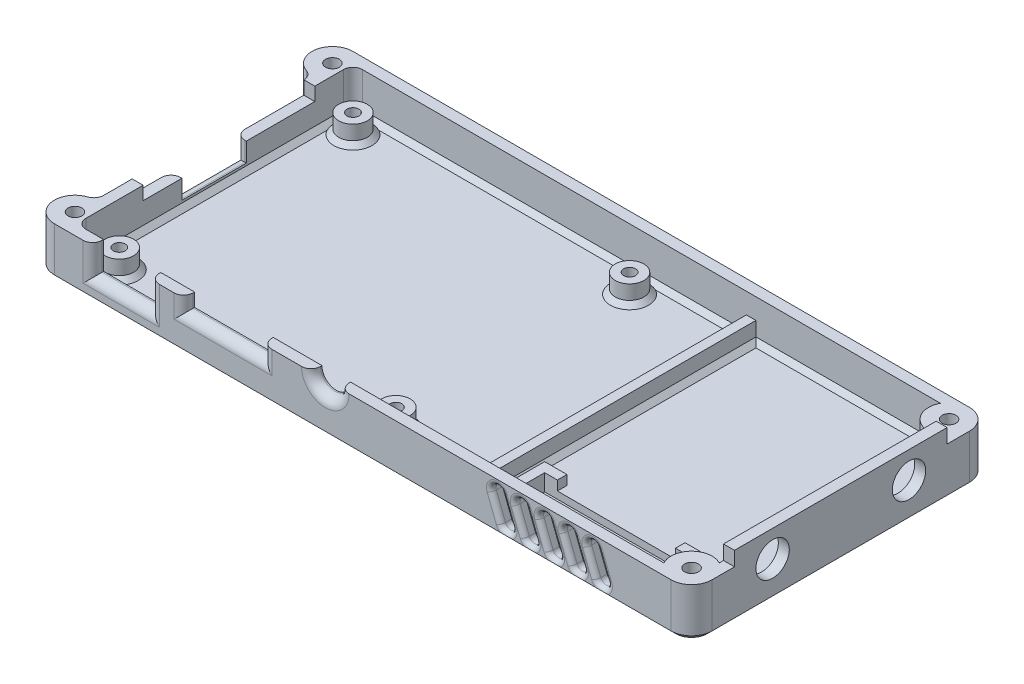
SolidWorks part; units mm, degrees
ref_plane "Front Plane" through (0, 0, 0) normal (0, 0, 1) x (1, 0, 0)
ref_plane "Top Plane" through (0, 0, 0) normal (0, 1, 0) x (1, 0, 0)
ref_plane "Right Plane" through (0, 0, 0) normal (1, 0, 0) x (0, 0, -1)
sketch "Sketch1" plane through (0, 0, 0) normal (0, 1, 0) x (1, 0, 0)
  line L0 (-71.5618, 3.106) -> (55.4382, 3.106) construction
  line L1 (-71.5618, 31.106) -> (55.4382, 31.106)
  line L2 (-71.5618, 31.106) -> (-71.5618, -24.894)
  line L3 (-71.5618, -24.894) -> (55.4382, -24.894)
  line L4 (55.4382, 31.106) -> (55.4382, -24.894)
  line L5 (-60.6618, -24.894) -> (-60.6618, -31.6828) construction
  line L6 (-68.0618, 27.606) -> (-10.0618, 27.606)
  line L7 (-68.0618, 27.606) -> (-68.0618, -21.394)
  line L8 (-68.0618, -21.394) -> (-10.0618, -21.394)
  line L9 (-10.0618, 27.606) -> (-10.0618, -21.394)
  line L10 (-39.5618, -24.894) -> (-39.5618, -31.6828) construction
  line L11 (-18.0618, -24.894) -> (-18.0618, -31.6828) construction
  line L12 (-65.4118, -26.5648) -> (-55.9118, -26.5648) construction
  line L13 (-48.0618, -26.5648) -> (-31.0618, -26.5648) construction
  line L14 (-22.0618, -26.5648) -> (-14.0618, -26.5648) construction
  line L15 (-72.5618, 9.606) -> (-72.5618, -3.394) construction
  line L16 (-71.5618, 3.106) -> (-72.5618, 3.106) construction
  dimension "D1" = 127
  dimension "D2" = 56
  dimension "D3" = 49
  dimension "D4" = 58
  dimension "D5" = 3.5
  dimension "D6" = 3.5
  dimension "D7" = 10.9
  dimension "D8" = 32
  dimension "D9" = 53.5
  dimension "D10" = 2
  dimension "D11" = 13
  dimension "D12" = 9.5
  dimension "D13" = 17
  dimension "D14" = 8
sketch "Sketch3" plane through (0, 0, 0) normal (0, 1, 0) x (1, 0, 0)
  line L4 (58.7382, 34.406) -> (-74.8618, 34.406)
  line L5 (-74.8618, 34.406) -> (-74.8618, -28.194)
  line L6 (-74.8618, -28.194) -> (58.7382, -28.194)
  line L7 (58.7382, -28.194) -> (58.7382, 34.406)
  line L8 (56.4382, 32.106) -> (-72.5618, 32.106)
  line L9 (56.4382, -25.894) -> (56.4382, 32.106)
  line L10 (-72.5618, -25.894) -> (56.4382, -25.894)
  line L11 (-72.5618, 32.106) -> (-72.5618, -25.894)
  line L12 (56.4382, 32.106) -> (-72.5618, 32.106)
  line L13 (56.4382, -25.894) -> (56.4382, 32.106)
  line L14 (-72.5618, -25.894) -> (56.4382, -25.894)
  line L15 (-72.5618, 32.106) -> (-72.5618, -25.894)
  line L16 (-8.0618, 3.106) -> (-8.0618, 34.406) construction
  line L17 (-71.5618, 3.106) -> (55.4382, 3.106) construction
  line L20 (-74.8618, 3.106) -> (52.7382, 3.106) construction
  line L25 (58.7382, -28.194) -> (58.7382, 34.406) construction
  line L26 (56.4382, -25.894) -> (56.4382, 32.106) construction
  dimension "D1" = 1
  dimension "D2" = 2.3
extrude "Boss-Extrude1" add sketch "Sketch3" along normal blind 10.3
sketch "Sketch5" plane through (0, 0, 0) normal (0, 1, 0) x (1, 0, 0)
  line L1 (-72.5618, 32.106) -> (56.4382, 32.106)
  line L2 (-72.5618, 32.106) -> (-72.5618, -25.894)
  line L3 (-72.5618, -25.894) -> (56.4382, -25.894)
  line L4 (56.4382, 32.106) -> (56.4382, -25.894)
extrude "Boss-Extrude2" add sketch "Sketch5" along normal blind 2
sketch "Sketch6" plane through (0, 2, 0) normal (0, 1, 0) x (1, 0, 0)
  circle A0 centre (-68.0618, 27.606) radius 3
  circle A1 centre (-68.0618, -21.394) radius 3
  circle A2 centre (-10.0618, -21.394) radius 3
  circle A3 centre (-10.0618, 27.606) radius 3
extrude "Boss-Extrude3" add sketch "Sketch6" along normal blind 4
hole_wizard "Ø2.5 (2.5) Diameter Hole1" positions "Sketch8" profile "Sketch9" hole size "Ø2.5" standard "ANSI Metric"
sketch "Sketch8" plane through (0, 6, 0) normal (0, 1, 0) x (1, 0, 0)
  point P0 (-68.0618, 27.606)
  point P3 (-10.0618, 27.606)
  point P6 (-10.0618, -21.394)
  point P9 (-68.0618, -21.394)
sketch "Sketch9" plane through (-68.0618, 6, -27.606) normal (1, 0, 0) x (0, 0, 1)
  line L0 (0, 0) -> (0, 8.7511)
  line L1 (0, 8.7511) -> (1.25, 8)
  line L2 (1.25, 8) -> (1.25, 0)
  line L5 (1.25, 0) -> (0, 0)
  line L10 (0, 8.7511) -> (-1.25, 8) construction
  line L11 (0, -6.35) -> (0, 107.95) construction
  dimension "Hole Dia." = 2.5
  dimension "Hole Depth" = 8
  dimension "Drill Angle" = 118
sketch "Sketch10" plane through (0, 2, 0) normal (0, 1, 0) x (1, 0, 0)
  line L0 (56.4382, 32.106) -> (-72.5618, 32.106) construction
  line L1 (9.9382, 32.106) -> (11.9382, 32.106)
  line L2 (9.9382, 32.106) -> (9.9382, -25.894)
  line L3 (9.9382, -25.894) -> (11.9382, -25.894)
  line L4 (11.9382, 32.106) -> (11.9382, -25.894)
  line L5 (-72.5618, -25.894) -> (56.4382, -25.894) construction
  line L6 (-10.0618, 27.606) -> (-10.0618, -21.394) construction
  dimension "D1" = 2
  dimension "D2" = 20
extrude "Boss-Extrude4" add sketch "Sketch10" along normal blind 4
sketch "Sketch11" plane through (0, 0, 28.194) normal (0, 0, 1) x (1, 0, 0)
  line L0 (-74.8618, 10.3) -> (-74.8618, 0) construction
  line L1 (-66.8618, 10.3) -> (-54.8618, 10.3)
  line L2 (-66.8618, 10.3) -> (-66.8618, 4.5)
  line L3 (-66.8618, 4.5) -> (-54.8618, 4.5)
  line L4 (-54.8618, 10.3) -> (-54.8618, 4.5)
  line L5 (-74.8618, 0) -> (58.7382, 0) construction
  line L6 (-60.8618, 10.3) -> (-60.6618, 0) construction
  line L7 (-65.4118, 0) -> (-55.9118, 0) construction
  line L9 (-47.778, 10.3) -> (-31.278, 10.3)
  line L10 (-47.778, 10.3) -> (-47.778, 7.5)
  line L11 (-47.778, 7.5) -> (-31.278, 7.5)
  line L12 (-31.278, 10.3) -> (-31.278, 7.5)
  line L13 (-68.0618, 0) -> (-10.0618, 0) construction
  line L14 (-39.5618, 0) -> (-39.528, 10.3) construction
  line L15 (-48.0618, 0) -> (-31.0618, 0) construction
  line L16 (-18.0618, 0) -> (-18.0618, 10.3) construction
  line L17 (-22.0618, 0) -> (-14.0618, 0) construction
  line L18 (-74.8618, 10.3) -> (58.7382, 10.3) construction
  circle A0 centre (-18.0618, 10.3) radius 3
  dimension "D5" = 6
  dimension "D1" = 4.5
  dimension "D2" = 12
  dimension "D3" = 7.5
  dimension "D4" = 16.5
  dimension "D6" = 8
extrude "Cut-Extrude1" cut sketch "Sketch11" against normal up to next
sketch "Sketch12" plane through (-74.8618, 0, 0) normal (-1, 0, 0) x (0, 0, 1)
  line L0 (-3.106, 0) -> (-3.106, 10.3) construction
  line L1 (-27.606, 0) -> (21.394, 0) construction
  line L2 (-34.406, 10.3) -> (28.194, 10.3) construction
  line L4 (-9.7329, 10.3) -> (3.7671, 10.3)
  line L5 (-9.7329, 10.3) -> (-9.7329, 3.5)
  line L6 (-9.7329, 3.5) -> (3.7671, 3.5)
  line L7 (3.7671, 10.3) -> (3.7671, 3.5)
  line L8 (-24.106, 10.3) -> (11.894, 10.3)
  line L9 (-24.106, 10.3) -> (-24.106, 7.5)
  line L10 (-24.106, 7.5) -> (11.894, 7.5)
  line L11 (11.894, 10.3) -> (11.894, 7.5)
  dimension "D1" = 13.5
  dimension "D2" = 3.5
  dimension "D3" = 7.5
  dimension "D4" = 36
extrude "Cut-Extrude2" cut sketch "Sketch12" against normal up to next contours L10 L11 L8 L9 | L7 L6 L5 L4
fillet "Fillet6" radius 2 1 edges at (56.4382, 6.15, -32.106)
fillet "Fillet8" radius 2 2 edges at (-72.5618, 6.15, 25.894) (-72.5618, 6.15, -32.106)
chamfer "Chamfer1" distance 1 angle 45 4 edges at (-68.0618, 2, 24.394) (-10.0618, 2, 24.394) (-10.0618, 2, -24.606) (-68.0618, 2, -24.606)
fillet "Fillet9" radius 2 9 edges at (-74.8618, 5.5, -9.7329) (-74.8618, 3.5, -2.9829) (-74.8618, 5.5, 3.7671) (-18.0618, 7.3, 28.194) (-31.278, 8.9, 28.194) (-47.778, 8.9, 28.194) (-39.528, 7.5, 28.194) (-54.8618, 7.4, 28.194) (-60.8618, 4.5, 28.194)
sketch "Sketch13" plane through (58.7382, 0, -61.1442) normal (1, 0, 0) x (0, 0, -1)
  line L0 (-89.3382, 10.3) -> (-89.3382, 0) construction
  line L1 (-26.7382, 10.3) -> (-26.7382, 0) construction
  circle A0 centre (-72.3382, 7.7223) radius 3.5
  circle A1 centre (-43.7382, 7.7223) radius 3.5
  dimension "D1" = 17
  dimension "D2" = 17
sketch "Sketch17" plane through (0, 0, 0) normal (0, 1, 0) x (1, 0, 0)
  line L0 (-74.8618, 34.406) -> (-74.8618, 24.106) construction
  line L1 (-74.8618, 34.406) -> (-74.8618, 25.806)
  line L2 (-74.8618, 25.806) -> (-74.659, 25.9406)
  line L3 (-74.8618, -19.594) -> (-74.8618, -28.194)
  line L4 (-74.8618, -28.194) -> (-74.659, -28.0594)
  arc A0 (-74.8618, -19.594) -> (-74.8618, -28.194) centre (-74.8618, -23.894) ccw
  arc A1 (-74.8618, 34.406) -> (-74.8618, 25.806) centre (-74.8618, 30.106) ccw
extrude "Boss-Extrude6" add sketch "Sketch17" along normal up to vertex (10.3 mm away) contours L1 A1 | L3 A0 region at (-76.6867, 0, -30.106) region at (-76.6867, 0, 23.894) up to point (-74.8618, 10.3, 28.194)
hole_wizard "Ø2.9 (2.9) Diameter Hole2" positions "Sketch19" profile "Sketch18" hole size "Ø2.9" standard "ANSI Metric" end condition up to next
sketch "Sketch19" plane through (0, 10.3, 0) normal (0, 1, 0) x (1, 0, 0)
  point P0 (-74.8618, 30.106)
sketch "Sketch18" plane through (-74.8618, 10.3, -30.106) normal (1, 0, 0) x (0, 0, 1)
  line L0 (0, 0) -> (0, 10.3)
  line L1 (0, 10.3) -> (1.45, 10.3)
  line L2 (1.45, 10.3) -> (1.45, 0)
  line L5 (1.45, 0) -> (0, 0)
  line L11 (0, -6.35) -> (0, 107.95) construction
  dimension "Thru Hole Dia." = 2.9
  dimension "Thru Hole Depth" = 10.3
hole_wizard "Ø2.9 (2.9) Diameter Hole1" positions "Sketch21" profile "Sketch20" hole size "Ø2.9" standard "ANSI Metric" end condition up to next
sketch "Sketch21" plane through (0, 10.3, 0) normal (0, 1, 0) x (1, 0, 0)
  point P0 (-74.8618, -23.894)
sketch "Sketch20" plane through (-74.8618, 10.3, 23.894) normal (1, 0, 0) x (0, 0, 1)
  line L0 (0, 0) -> (0, 10.3)
  line L1 (0, 10.3) -> (1.45, 10.3)
  line L2 (1.45, 10.3) -> (1.45, 0)
  line L5 (1.45, 0) -> (0, 0)
  line L11 (0, -6.35) -> (0, 107.95) construction
  dimension "Thru Hole Dia." = 2.9
  dimension "Thru Hole Depth" = 10.3
sketch "Sketch24" plane through (0, 2, 0) normal (0, 1, 0) x (1, 0, 0)
  line L0 (11.9382, 3.106) -> (61.5789, 3.106) construction
  line L1 (11.9382, -25.894) -> (11.9382, 32.106) construction
  line L2 (58.7382, -28.194) -> (58.7382, 34.406) construction
  circle A0 centre (54.4382, -23.894) radius 4.3
  circle A1 centre (54.4382, 30.106) radius 4.3
  dimension "D1" = 4.3
extrude "Boss-Extrude7" add sketch "Sketch24" along normal up to surface (8.3 mm away) up to face at (-74.8618, 10.3, 25.344)
hole_wizard "Ø2.9 (2.9) Diameter Hole5" positions "Sketch31" profile "Sketch30" hole size "Ø2.9" standard "ANSI Metric" end condition up to next
sketch "Sketch31" plane through (0, 10.3, 0) normal (0, 1, 0) x (1, 0, 0)
  point P0 (54.4382, -23.894)
sketch "Sketch30" plane through (54.4382, 10.3, 23.894) normal (1, 0, 0) x (0, 0, 1)
  line L0 (0, 0) -> (0, 10.3)
  line L1 (0, 10.3) -> (1.45, 10.3)
  line L2 (1.45, 10.3) -> (1.45, 0)
  line L5 (1.45, 0) -> (0, 0)
  line L11 (0, -6.35) -> (0, 107.95) construction
  dimension "Thru Hole Dia." = 2.9
  dimension "Thru Hole Depth" = 10.3
hole_wizard "Ø2.9 (2.9) Diameter Hole4" positions "Sketch28" profile "Sketch27" hole size "Ø2.9" standard "ANSI Metric" end condition up to next
sketch "Sketch28" plane through (0, 10.3, 0) normal (0, 1, 0) x (1, 0, 0)
  point P0 (54.4382, 30.106)
sketch "Sketch27" plane through (54.4382, 10.3, -30.106) normal (1, 0, 0) x (0, 0, 1)
  line L0 (0, 0) -> (0, 10.3)
  line L1 (0, 10.3) -> (1.45, 10.3)
  line L2 (1.45, 10.3) -> (1.45, 0)
  line L5 (1.45, 0) -> (0, 0)
  line L11 (0, -6.35) -> (0, 107.95) construction
  dimension "Thru Hole Dia." = 2.9
  dimension "Thru Hole Depth" = 10.3
fillet "Fillet10" radius 4.3 1 edges at (58.7382, 5.15, -34.406)
fillet "Fillet18" radius 2 2 edges at (-74.8618, 5.15, 19.594) (-74.8618, 5.15, -25.806)
chamfer "Chamfer3" distance 1 angle 45 9 edges at (57.4788, 0, -33.1466) (-10.2118, 0, -34.406) (58.7382, 0, -0.956) (-79.1058, 0, -30.7975) (-75.2385, 0, -25.3002) (-74.8618, 0, -3.106) (-75.2385, 0, 19.0883) (-79.1058, 0, 24.5855) (-8.0618, 0, 28.194)
fillet "Fillet19" radius 2 1 edges at (-66.8618, 6.4, 28.194)
fillet "Fillet20" radius 4.3 1 edges at (58.7382, 5.65, 28.194)
chamfer "Chamfer5" distance 1 angle 45 8 edges at (-72.5618, 2, -3.106) (-71.976, 2, 25.3082) (-71.976, 2, -31.5202) (-30.3118, 2, 25.894) (-30.3118, 2, -32.106) (9.9382, 2, -3.106) (11.9382, 2, -3.106) (31.2849, 2, -32.106)
chamfer "Chamfer6" distance 1 angle 45 1 edges at (56.4382, 2, -3.106)
sketch "Sketch29" plane through (0, 10.3, 0) normal (0, 1, 0) x (1, 0, 0)
  line L0 (56.4382, -20.0874) -> (56.4382, 26.2994) construction
  line L1 (56.4382, 25.406) -> (58.7382, 25.406)
  line L2 (56.4382, 25.406) -> (56.4382, -19.194)
  line L3 (56.4382, -19.194) -> (58.7382, -19.194)
  line L4 (58.7382, 25.406) -> (58.7382, -19.194)
  line L5 (58.7382, -23.894) -> (58.7382, 30.106) construction
  line L6 (54.4382, 34.406) -> (-74.8618, 34.406) construction
  line L7 (-13.0618, -28.194) -> (54.4382, -28.194) construction
  dimension "D1" = 9
  dimension "D2" = 9
extrude "Boss-Extrude8" add sketch "Sketch29" along normal blind 3
extrude "Cut-Extrude3" cut sketch "Sketch13" against normal up to next
sketch "Sketch32" plane through (0, 2, 0) normal (0, 1, 0) x (1, 0, 0)
  line L0 (12.9382, -25.894) -> (50.6317, -25.894) construction
  line L1 (15.4382, -15.694) -> (45.5382, -15.694)
  line L2 (15.4382, -15.694) -> (15.4382, -25.894)
  line L3 (15.4382, -25.894) -> (45.5382, -25.894)
  line L4 (45.5382, -15.694) -> (45.5382, -25.894)
  line L5 (-72.5618, -23.894) -> (-72.5618, 30.106) construction
  dimension "D1" = 10.2
  dimension "D2" = 30.1
  dimension "D3" = 88
extrude "Cut-Extrude4" cut sketch "Sketch32" against normal blind 1.5
sketch "Sketch33" plane through (0, 2, 0) normal (0, 1, 0) x (1, 0, 0)
  line L0 (15.4382, -15.694) -> (15.4382, -25.894)
  line L2 (15.4382, -25.894) -> (13.4382, -25.894)
  line L3 (12.9382, -25.894) -> (15.4382, -25.894) construction
  line L4 (47.5382, -13.694) -> (47.5382, -20.8822)
  line L5 (47.5382, -20.8822) -> (45.5382, -20.8822)
  line L6 (45.5382, -25.894) -> (45.5382, -20.7012) construction
  line L7 (45.5382, -20.8822) -> (45.5382, -15.694)
  line L8 (30.4882, -15.694) -> (30.4882, -23.4127) construction
  line L9 (45.5382, -15.694) -> (15.4382, -15.694) construction
  line L10 (18.1083, -13.694) -> (18.1083, -15.694)
  line L11 (42.8681, -13.694) -> (42.8681, -15.694)
  line L12 (13.4382, -13.694) -> (13.4382, -27.894)
  line L13 (13.4382, -27.894) -> (47.5382, -27.894)
  line L14 (47.5382, -27.894) -> (47.5382, -13.694)
  line L15 (47.5382, -13.694) -> (13.4382, -13.694)
  line L16 (13.4382, -13.694) -> (13.4382, -25.894)
  line L17 (45.5382, -15.694) -> (42.8681, -15.694)
  line L19 (47.5382, -13.694) -> (42.8681, -13.694)
  line L20 (18.1083, -13.694) -> (13.4382, -13.694)
  line L21 (18.1083, -15.694) -> (15.4382, -15.694)
  dimension "D1" = 2
extrude "Boss-Extrude9" add sketch "Sketch33" along normal blind 2
sketch "Sketch34" plane through (0, 0, 28.194) normal (0, 0, 1) x (1, 0, 0)
  line L0 (17.9748, 7.7443) -> (19.8911, 2.8029) construction
  line L1 (19.1402, 8.1963) -> (21.0565, 3.2549)
  line L2 (16.8093, 7.2924) -> (18.7256, 2.3509)
  line L3 (22.9748, 7.7443) -> (24.8911, 2.8029) construction
  line L4 (24.1402, 8.1963) -> (26.0565, 3.2549)
  line L5 (21.8093, 7.2924) -> (23.7256, 2.3509)
  line L6 (27.9748, 7.7443) -> (29.8911, 2.8029) construction
  line L7 (29.1402, 8.1963) -> (31.0565, 3.2549)
  line L8 (26.8093, 7.2924) -> (28.7256, 2.3509)
  line L9 (32.9748, 7.7443) -> (34.8911, 2.8029) construction
  line L10 (34.1402, 8.1963) -> (36.0565, 3.2549)
  line L11 (31.8093, 7.2924) -> (33.7256, 2.3509)
  line L12 (37.9748, 7.7443) -> (39.8911, 2.8029) construction
  line L13 (39.1402, 8.1963) -> (41.0565, 3.2549)
  line L14 (36.8093, 7.2924) -> (38.7256, 2.3509)
  arc A0 (19.1402, 8.1963) -> (16.8093, 7.2924) centre (17.9748, 7.7443) ccw
  arc A1 (18.7256, 2.3509) -> (21.0565, 3.2549) centre (19.8911, 2.8029) ccw
  arc A2 (24.1402, 8.1963) -> (21.8093, 7.2924) centre (22.9748, 7.7443) ccw
  arc A3 (23.7256, 2.3509) -> (26.0565, 3.2549) centre (24.8911, 2.8029) ccw
  arc A4 (29.1402, 8.1963) -> (26.8093, 7.2924) centre (27.9748, 7.7443) ccw
  arc A5 (28.7256, 2.3509) -> (31.0565, 3.2549) centre (29.8911, 2.8029) ccw
  arc A6 (34.1402, 8.1963) -> (31.8093, 7.2924) centre (32.9748, 7.7443) ccw
  arc A7 (33.7256, 2.3509) -> (36.0565, 3.2549) centre (34.8911, 2.8029) ccw
  arc A8 (39.1402, 8.1963) -> (36.8093, 7.2924) centre (37.9748, 7.7443) ccw
  arc A9 (38.7256, 2.3509) -> (41.0565, 3.2549) centre (39.8911, 2.8029) ccw
  point P2 (18.9329, 5.2736)
  point P9 (23.9329, 5.2736)
  point P16 (28.9329, 5.2736)
  point P23 (33.9329, 5.2736)
  point P30 (38.9329, 5.2736)
extrude "Cut-Extrude5" cut sketch "Sketch34" against normal up to next
fillet "Fillet21" radius 1 20 edges at (37.5228, 8.9098, 28.194) (40.0983, 5.7256, 28.194) (40.343, 1.6375, 28.194) (32.5228, 8.9098, 28.194) (35.0983, 5.7256, 28.194) (35.343, 1.6375, 28.194) (27.5228, 8.9098, 28.194) (30.0983, 5.7256, 28.194) (30.343, 1.6375, 28.194) (22.5228, 8.9098, 28.194) (25.0983, 5.7256, 28.194) (25.343, 1.6375, 28.194) (17.5228, 8.9098, 28.194) (20.0983, 5.7256, 28.194) (20.343, 1.6375, 28.194) (37.7675, 4.8217, 28.194) (32.7675, 4.8217, 28.194) (27.7675, 4.8217, 28.194) (22.7675, 4.8217, 28.194) (17.7675, 4.8217, 28.194)
chamfer "Chamfer7" distance 1 angle 45 1 edges at (57.4788, 0, 26.9346)
